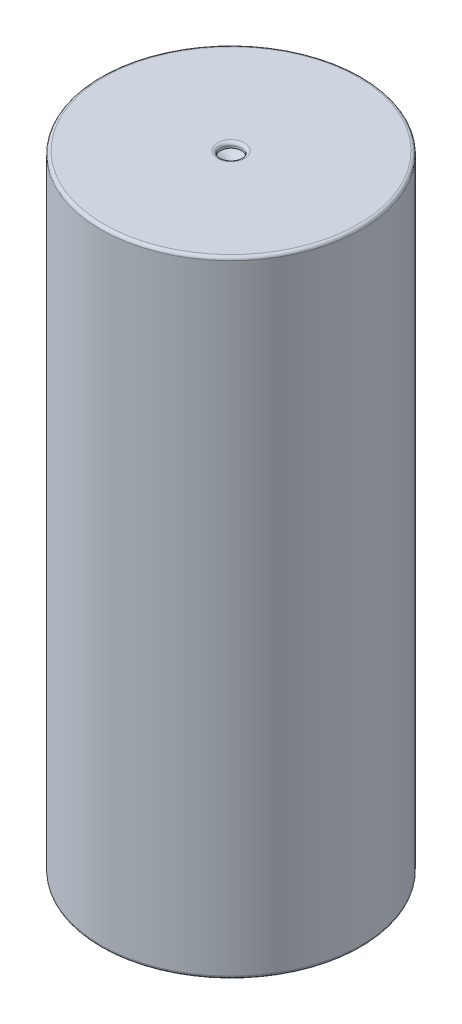
SolidWorks part; units mm, degrees
ref_plane "Front Plane" through (0, 0, 0) normal (0, 0, 1) x (1, 0, 0)
ref_plane "Top Plane" through (0, 0, 0) normal (0, 1, 0) x (1, 0, 0)
ref_plane "Right Plane" through (0, 0, 0) normal (1, 0, 0) x (0, 0, -1)
sketch "Sketch2" plane through (0, 0, 0) normal (0, 0, 1) x (1, 0, 0)
  line L5 (12.5, 30) -> (0, 30)
  line L6 (12.5, 30) -> (12.5, -30)
  line L7 (12.5, -30) -> (0, -30)
  line L8 (0, 30) -> (0, -30)
  line L9 (12.5, 30) -> (0, -30) construction
  line L10 (12.5, -30) -> (0, 30) construction
  point P0 (6.25, 0)
  point P6 (0, 0)
  dimension "D1" = 12.5
  dimension "D2" = 60
revolve "Revolve1" add sketch "Sketch2" angle 360 about L8
sketch "Sketch4" plane through (0, 0, 0) normal (0, 0, 1) x (1, 0, 0)
  line L0 (0, 30) -> (0, 29)
  line L1 (12.5, 30) -> (-12.5, 30) construction
  line L2 (0, 29) -> (1, 29.5)
  line L3 (1, 29.5) -> (1, 30)
  line L4 (1, 30) -> (0, 30)
  dimension "D1" = 1
  dimension "D2" = 1
  dimension "D3" = 0.5
revolve "Cut-Revolve1" cut sketch "Sketch4" angle 360 about L0
mirror "Mirror2" about plane through (0, 0, 0) normal (0, 1, 0) of "Cut-Revolve1"
fillet "Fillet1" radius 0.3 4 edges at (0, 30, 12.5) (-1, 30, 0) (0, -30, 12.5) (-1, -30, 0)
ref_axis "Axis1" through (0, -29.7, 0) along (0, 1, 0)
